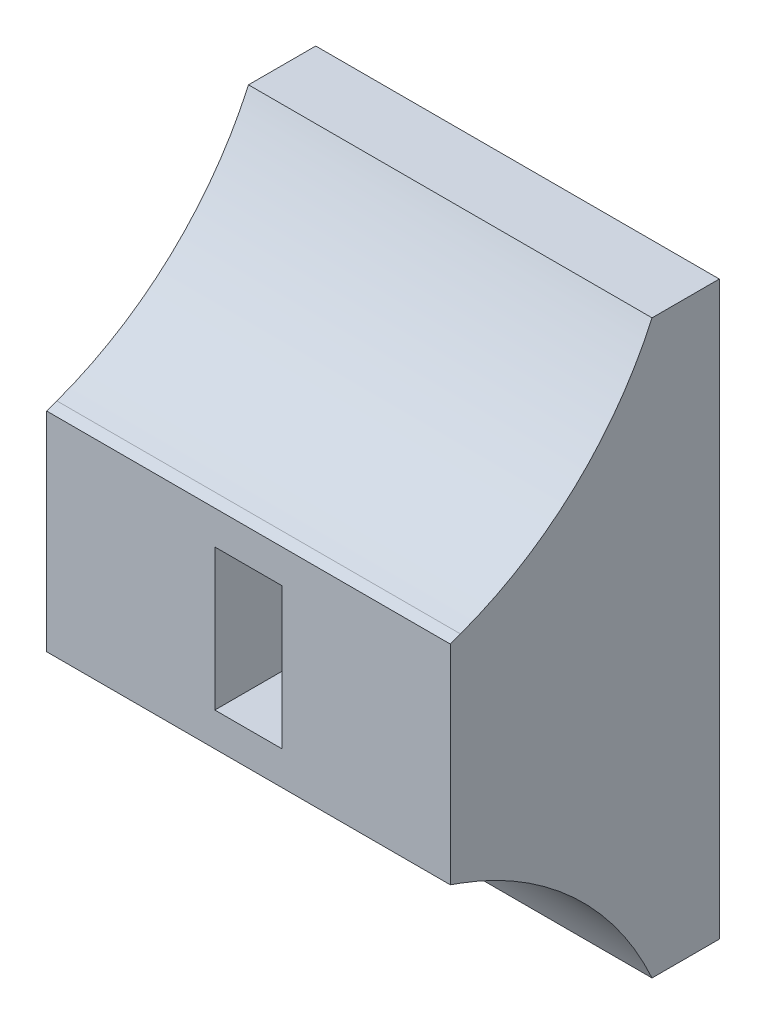
SolidWorks part; units mm, degrees
ref_plane "Спереди" through (0, 0, 0) normal (0, 0, 1) x (1, 0, 0)
ref_plane "Сверху" through (0, 0, 0) normal (0, 1, 0) x (1, 0, 0)
ref_plane "Справа" through (0, 0, 0) normal (1, 0, 0) x (0, 0, -1)
sketch "Sketch1" plane through (0, 0, 0) normal (0, 0, 1) x (1, 0, 0)
  line L1 (-6, -8.5) -> (6, -8.5)
  line L2 (-6, -8.5) -> (-6, 8.5)
  line L3 (-6, 8.5) -> (6, 8.5)
  line L4 (6, -8.5) -> (6, 8.5)
  line L5 (-6, -8.5) -> (6, 8.5) construction
  line L6 (-6, 8.5) -> (6, -8.5) construction
  line L7 (-1, -2.1) -> (1, -2.1)
  line L8 (-1, -2.1) -> (-1, 2.1)
  line L9 (-1, 2.1) -> (1, 2.1)
  line L10 (1, -2.1) -> (1, 2.1)
  line L11 (-1, -2.1) -> (1, 2.1) construction
  line L12 (-1, 2.1) -> (1, -2.1) construction
  point P0 (0, 0)
  point P6 (0, 0)
  dimension "D1" = 12
  dimension "D2" = 17
  dimension "D3" = 2
  dimension "D4" = 4.2
extrude "Extrude1" add sketch "Sketch1" along normal blind 8
sketch "Sketch2" plane through (-6, 0, 0) normal (-1, 0, 0) x (0, 0, 1)
  line L0 (2, 8.5) -> (3.3493, 4.7927)
  line L1 (8, 8.5) -> (0, 8.5) construction
  line L2 (3.3493, 4.7927) -> (8, 3.1)
  line L3 (8, 8.5) -> (8, -8.5) construction
  line L4 (8, 3.1) -> (8, 8.5)
  line L5 (8, 8.5) -> (2, 8.5)
  dimension "D1" = 6
  dimension "D2" = 70
  dimension "D3" = 1
  dimension "D4" = 70
extrude "Extrude2" cut sketch "Sketch2" against normal through all
mirror "Mirror1" about plane through (0, 0, 0) normal (0, 1, 0) of "Extrude2"
fillet "Fillet1" radius 10 2 edges at (0, -4.7927, 3.3493) (0, 4.7927, 3.3493)
